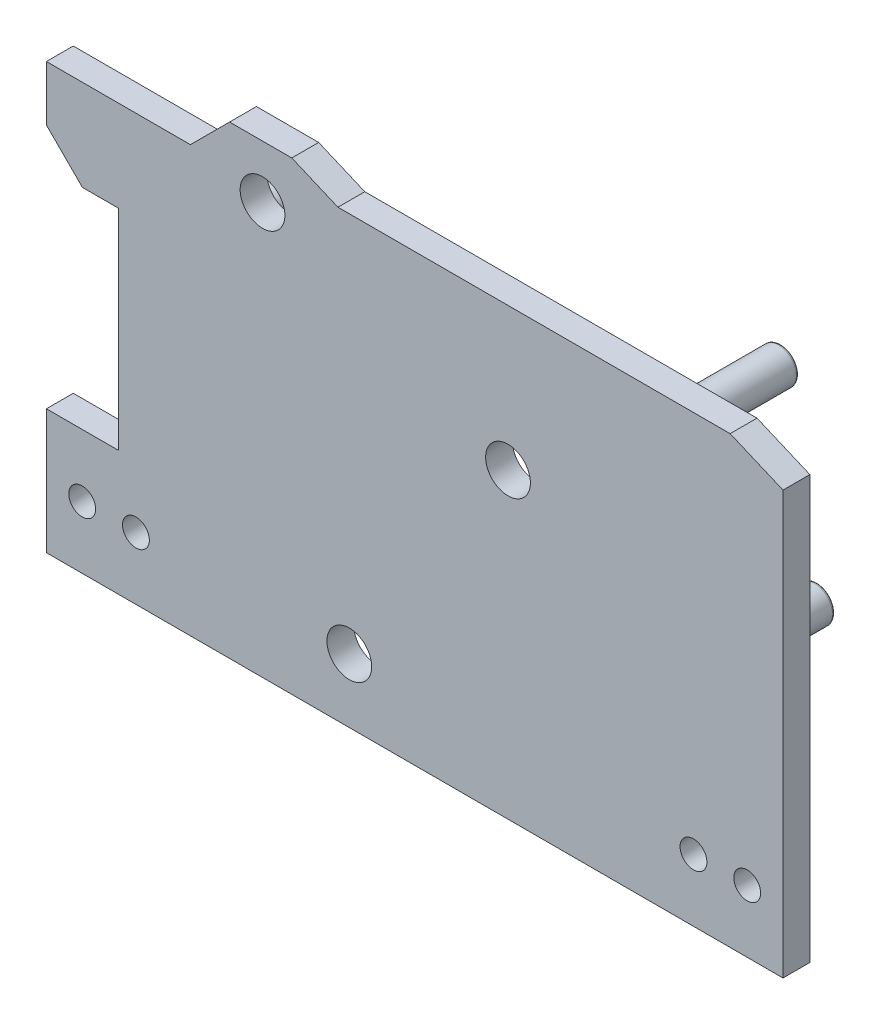
SolidWorks part; units mm, degrees
ref_plane "정면" through (0, 0, 0) normal (0, 0, 1) x (1, 0, 0)
ref_plane "윗면" through (0, 0, 0) normal (0, 1, 0) x (1, 0, 0)
ref_plane "우측면" through (0, 0, 0) normal (1, 0, 0) x (0, 0, -1)
sketch "스케치2" plane through (0, 0, 0) normal (0, 0, 1) x (1, 0, 0)
  line L0 (-41.986, 21.4677) -> (-25.9008, 21.4677)
  line L1 (-25.9008, 21.4677) -> (-21.5254, 25.8432)
  line L2 (-21.5254, 25.8432) -> (-14.5764, 25.8432)
  line L3 (-14.5764, 25.8432) -> (-9.4218, 23.6554)
  line L4 (-9.4218, 23.6554) -> (34.3842, 23.6554)
  line L5 (34.3842, 23.6554) -> (40.2906, 21.1486)
  line L6 (40.2906, 21.1486) -> (40.2906, -26.0481)
  line L7 (40.2906, -26.0481) -> (-41.986, -26.0481)
  line L8 (-41.986, -26.0481) -> (-41.986, -12.1234)
  line L9 (-41.986, -12.1234) -> (-33.9434, -12.1234)
  line L10 (-33.9434, -12.1234) -> (-33.9434, 11.3014)
  line L11 (-33.9434, 11.3014) -> (-37.9647, 11.3014)
  line L12 (-37.9647, 11.3014) -> (-41.986, 15.3227)
  line L13 (-41.986, 15.3227) -> (-41.986, 21.4677)
  line L14 (24.6957, -6.2695) -> (30.5742, -6.2695)
  line L15 (31.5742, -5.2695) -> (31.5742, 0.609)
  line L16 (31.2814, -5.9766) -> (25.9521, -0.6474) construction
  line L17 (-0.8477, -0.8025) -> (-17.8477, -0.8025) construction
  line L18 (-17.8477, -0.8025) -> (-17.8477, 19.8975) construction
  circle A0 centre (-17.8477, 19.8975) radius 2.5
  circle A1 centre (-29.1621, 7.8743) radius 4
  circle A2 centre (24.5742, 17.7305) radius 4
  circle A3 centre (-8.1538, -18.91) radius 2.5
  circle A4 centre (9.5742, 7.7305) radius 2.5
  circle A5 centre (-29.1621, 7.8743) radius 2
  circle A6 centre (24.5742, 17.7305) radius 2
  arc A7 (30.4304, 1.5986) -> (23.7061, -5.1256) centre (31.5742, -6.2695) ccw
  arc A8 (30.5742, -6.2695) -> (31.5742, -5.2695) centre (30.5742, -5.2695) ccw
  arc A9 (31.5742, 0.609) -> (30.4304, 1.5986) centre (30.5742, 0.609) ccw
  arc A10 (24.6957, -6.2695) -> (23.7061, -5.1256) centre (24.6957, -5.2695) cw
  circle A11 centre (28.6167, -3.312) radius 2
  dimension "D1" = 1
  dimension "D5" = 5
  dimension "D6" = 5
  dimension "D7" = 5
  dimension "D12" = 4
  dimension "D13" = 4
  dimension "D14" = 8
  dimension "D15" = 8
  dimension "D18" = 4
  dimension "D2" = 30
  dimension "D3" = 40
  dimension "D4" = 32
  dimension "D8" = 20.7
  dimension "D9" = 17
  dimension "D10" = 10
  dimension "D11" = 15
  dimension "D16" = 22
  dimension "D17" = 14
extrude "보스-돌출11" add sketch "스케치2" along normal blind 3 contours A5 | A1 A5 | L13 L12 L11 L10 L9 L8 L7 L6 L5 L4 L3 L2 L1 L0 A4 A3 A2 A1 A0 L14 A10 A7 A9 L15 A8 | A2 A6 | A6 | A11 | A10 L14 A8 L15 A9 A7 A11 region at (1.0264, -1.8236, 0) region at (24.0237, -5.8509, 0) region at (-33.049, 7.8743, 0) region at (20.6874, 17.7305, 0) region at (-29.1621, 7.8743, 0) region at (24.5742, 17.7305, 0) region at (28.6167, -3.312, 0)
extrude "보스-돌출12" add sketch "스케치2<16>" against normal blind 0.5 contours A1 A5 | A2 A6 | A10 L14 A8 L15 A9 A7 A11 region at (24.0237, -5.8509, 0) region at (-33.049, 7.8743, 0) region at (20.6874, 17.7305, 0)
sketch "스케치2<16>" plane through (0, 0, 0) normal (0, 0, 1) x (1, 0, 0) same geometry as "스케치2"
extrude "보스-돌출13" add sketch "스케치2<17>" against normal blind 12.5 contours A11 | A6 | A5 region at (-29.1621, 7.8743, 0) region at (24.5742, 17.7305, 0) region at (28.6167, -3.312, 0)
sketch "스케치2<17>" plane through (0, 0, 0) normal (0, 0, 1) x (1, 0, 0) same geometry as "스케치2"
fillet "필렛1" radius 0.3 3 edges at (30.6167, -3.312, -12.5) (26.5742, 17.7305, -12.5) (-27.1621, 7.8743, -12.5)
sketch "스케치3" plane through (0, 0, 0) normal (0, 0, -1) x (-1, 0, 0)
  line L0 (-40.2906, 21.1486) -> (-40.2906, -26.0481) construction
  line L1 (-40.2906, -26.0481) -> (41.986, -26.0481) construction
  line L2 (41.986, -26.0481) -> (41.986, -12.1234) construction
  line L3 (-40.2906, -26.0481) -> (41.986, -26.0481) construction
  circle A0 centre (-36.2906, -19.0881) radius 1.5
  circle A1 centre (-30.2906, -19.0881) radius 1.5
  circle A2 centre (31.986, -19.0881) radius 1.5
  circle A3 centre (37.986, -19.0881) radius 1.5
  dimension "D1" = 3
  dimension "D2" = 3
  dimension "D7" = 3
  dimension "D8" = 3
  dimension "D3" = 6
  dimension "D4" = 4
  dimension "D5" = 6.96
  dimension "D6" = 6.96
  dimension "D9" = 6
  dimension "D10" = 4
  dimension "D11" = 6.96
  dimension "D12" = 6.96
extrude "컷-돌출1" cut sketch "스케치3" against normal up to next
